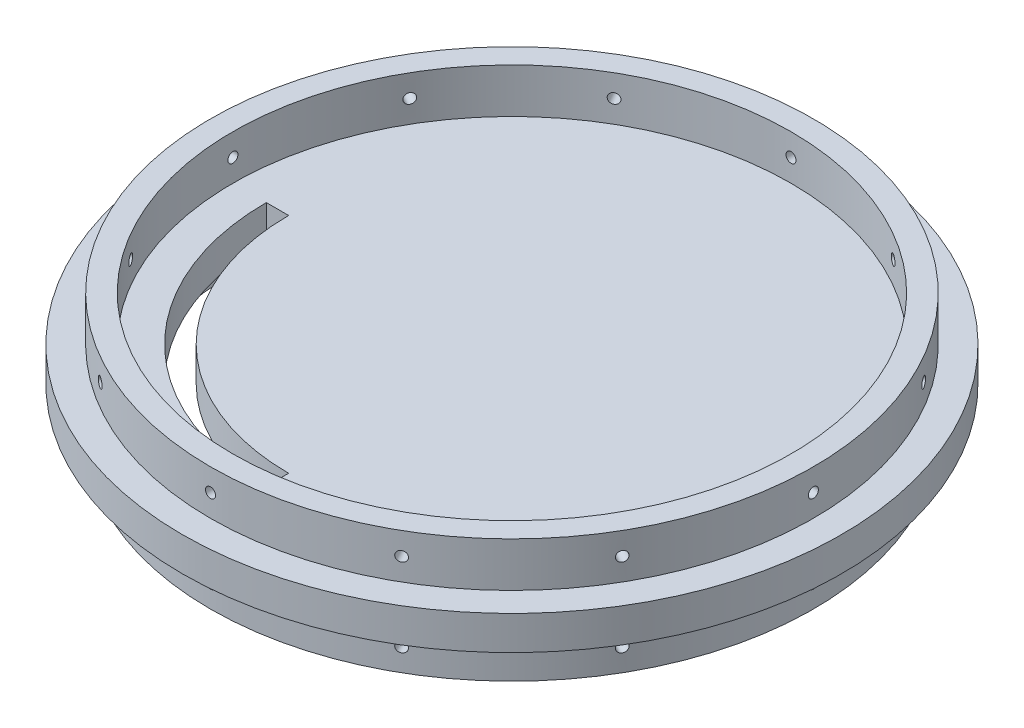
SolidWorks part; units mm, degrees
material "6061-T6 (SS)"
ref_plane "Front Plane" through (0, 0, 0) normal (0, 0, 1) x (1, 0, 0)
ref_plane "Top Plane" through (0, 0, 0) normal (0, 1, 0) x (1, 0, 0)
ref_plane "Right Plane" through (0, 0, 0) normal (1, 0, 0) x (0, 0, -1)
sketch "Sketch1" plane through (0, 0, 0) normal (0, 1, 0) x (1, 0, 0)
  circle A0 centre (0, 0) radius 93.726
  dimension "D1" = 187.452
extrude "Boss-Extrude1" add sketch "Sketch1" along normal mid plane 9.652
sketch "Sketch2" plane through (0, 0, 0) normal (0, 0, 1) x (1, 0, 0)
  line L0 (0, -18.3275) -> (0, 20.8308) construction
  line L1 (0, -4.826) -> (-19.297, -4.826)
  line L2 (-93.726, -4.826) -> (93.726, -4.826) construction
  line L3 (0, -4.826) -> (0, -1.4952)
  line L4 (-0.3818, -1.4952) -> (0, -1.4952)
  arc A0 (-19.297, -4.826) -> (-0.3818, -1.4952) centre (-0.4072, -56.7254) cw
  dimension "D6" = 55.2302
  dimension "D1" = 19.297
  dimension "D2" = 3.3308
  dimension "D3" = 0.3818
revolve "Cut-Revolve1" cut sketch "Sketch2" angle 360 about L0
sketch "Sketch4" plane through (0, 4.826, 0) normal (0, 1, 0) x (1, 0, 0)
  circle A0 centre (0, 0) radius 85.725
  circle A1 centre (0, 0) radius 79.375
  dimension "D1" = 171.45
  dimension "D2" = 158.75
extrude "Boss-Extrude2" add sketch "Sketch4" along normal blind 12.7
ref_plane "Plane1" through (0, 0, -85.725) normal (0, 0, -1) x (-1, 0, 0)
sketch "Sketch5" plane through (0, 0, -85.725) normal (0, 0, -1) x (-1, 0, 0)
  line L0 (0, 19.2786) -> (0, -19.2786) construction
  line L1 (79.375, 17.526) -> (-79.375, 17.526) construction
  circle A0 centre (0, 11.176) radius 1.4351
  dimension "D1" = 2.8702
  dimension "D2" = 6.35
extrude "Cut-Extrude2" cut sketch "Sketch5" against normal blind 12.7
pattern_circular "CirPattern1" count 12 over 360 about axis through (0, 17.526, 0) along (0, -1, 0) of "Cut-Extrude2" reverse direction yes
mirror "Mirror2" about plane through (0, 0, 0) normal (0, 1, 0) of "CirPattern1", "Cut-Extrude2", "Boss-Extrude2"
sketch "Sketch6" plane through (0, 4.826, 0) normal (0, 1, 0) x (1, 0, 0)
  line L0 (-63.5, 0) -> (-69.85, 0)
  line L1 (0, -69.85) -> (0, -63.5)
  line L2 (0, -12.2936) -> (0, 12.2936) construction
  arc A0 (-69.85, 0) -> (0, -69.85) centre (0, 0) ccw
  arc A1 (-63.5, 0) -> (0, -63.5) centre (0, 0) ccw
  dimension "D1" = 69.85
  dimension "D2" = 63.5
  dimension "D3" = 90
extrude "Cut-Extrude3" cut sketch "Sketch6" against normal up to surface (9.652 mm away) up to face at (0, -4.826, -19.297)
